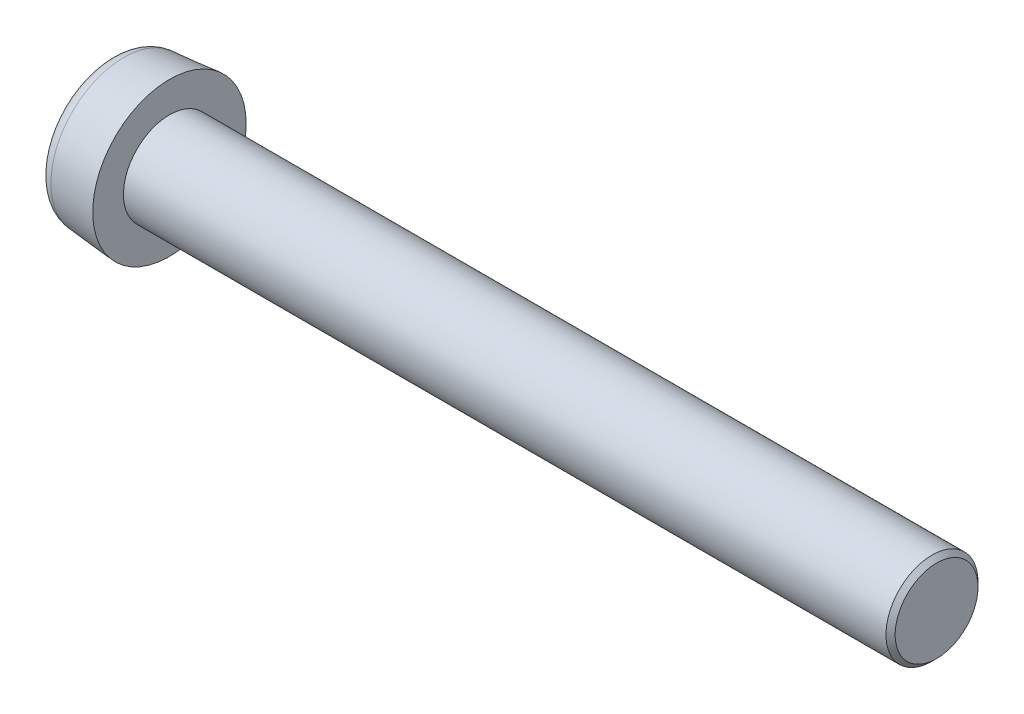
SolidWorks part; units mm, degrees
ref_plane "Front" through (0, 0, 0) normal (0, 0, 1) x (1, 0, 0)
ref_plane "Top" through (0, 0, 0) normal (0, 1, 0) x (1, 0, 0)
ref_plane "Right" through (0, 0, 0) normal (1, 0, 0) x (0, 0, -1)
ref_plane "Plane1" through (3.9, 0, 0) normal (1, 0, 0) x (0, 0, -1)
sketch "Sketch1" plane through (3.9, 0, 0) normal (1, 0, 0) x (0, 0, -1)
  circle A0 centre (0, 0) radius 5
  dimension "dk" = 10
extrude "BaseHead" add sketch "Sketch1" against normal blind 3.9 draft 5
sketch "Sketch2" plane through (3.9, 0, 0) normal (1, 0, 0) x (0, 0, -1)
  circle A0 centre (0, 0) radius 3
extrude "BaseBody" add sketch "Sketch2" along normal blind 50
cosmetic thread "ThreadCosmetic1" parameters "bb"=24, "THD_MINOR"=4.917
fillet "HeadFillet" [suppressed] radius 0.25
sketch "Sketch3" plane through (0, 0, 0) normal (1, 0, 0) x (0, 0, -1)
  line L1 (2.396, 0) -> (1.198, 2.075)
  line L2 (1.198, 2.075) -> (-1.198, 2.075)
  line L3 (-1.198, 2.075) -> (-2.396, 0)
  line L4 (-2.396, 0) -> (-1.198, -2.075)
  line L5 (-1.198, -2.075) -> (1.198, -2.075)
  line L6 (1.198, -2.075) -> (2.396, 0)
  circle A0 centre (0, 0) radius 2.075 construction
  dimension "B" = 4.15
extrude "HexagonSocket" cut sketch "Sketch3" along normal blind 2
sketch "Sketch4" plane through (2, 0, 0) normal (-1, 0, 0) x (0, 0, 1)
  line L0 (1.198, -2.075) -> (-1.198, -2.075) construction
  line L1 (-1.198, -2.075) -> (-2.396, 0) construction
  line L2 (-2.396, 0) -> (-1.198, 2.075) construction
  line L3 (2.396, 0) -> (1.198, -2.075) construction
  line L4 (1.198, 2.075) -> (2.396, 0) construction
  line L5 (-1.198, 2.075) -> (1.198, 2.075) construction
  line L6 (1.198, -2.075) -> (-1.198, -2.075)
  line L7 (-1.198, -2.075) -> (-2.396, 0)
  line L8 (-2.396, 0) -> (-1.198, 2.075)
  line L9 (2.396, 0) -> (1.198, -2.075)
  line L10 (1.198, 2.075) -> (2.396, 0)
  line L11 (-1.198, 2.075) -> (1.198, 2.075)
extrude "Cut-Extrude2" cut sketch "Sketch4" against normal blind 5 draft 60
fillet "TopFillet" radius 1 1 edges at (0, 0, -4.6588)
chamfer "Chamfer1" distance 0.3 angle 45 1 edges at (53.9, 0, -3)
sketch "Sketch5" plane through (0, 0, 0) normal (0, 0, 1) x (1, 0, 0)
  line L0 (53.6, 2.531) -> (53.8708, 3)
  line L1 (53.8708, 3) -> (53.8708, 3.5415)
  line L2 (53.8708, 3.5415) -> (53.3293, 3.5415)
  line L3 (53.3293, 3.5415) -> (53.3293, 3)
  line L4 (53.3293, 3) -> (53.6, 2.531)
  line L5 (0, 0) -> (26.2596, 0) construction
  line L6 (53.6, -3) -> (53.6, 3) construction
  dimension "D1" = 0.5415
  dimension "D2" = 6
revolve "Cut-Revolve10" [suppressed] cut sketch "Sketch5" angle 360 about L5
pattern_linear "LPattern10" [suppressed] count 37 spacing 0.6498 along (-1, 0, 0) of bodies 105
equation "\"D1@Plane1\" = \"K@BaseHead\""
equation "\"D2@Sketch5\" = \"d@Sketch2\""
equation "\"D1@Sketch5\" =  ( \"d@Sketch2\" - \"THD_MINOR@ThreadCosmetic1\" )  / 2"
equation "\"D3@LPattern10\" = \"D1@Sketch5\" * 1.2"
equation "\"D1@LPattern10\" = \"bb@ThreadCosmetic1\" / \"D3@LPattern10\""
